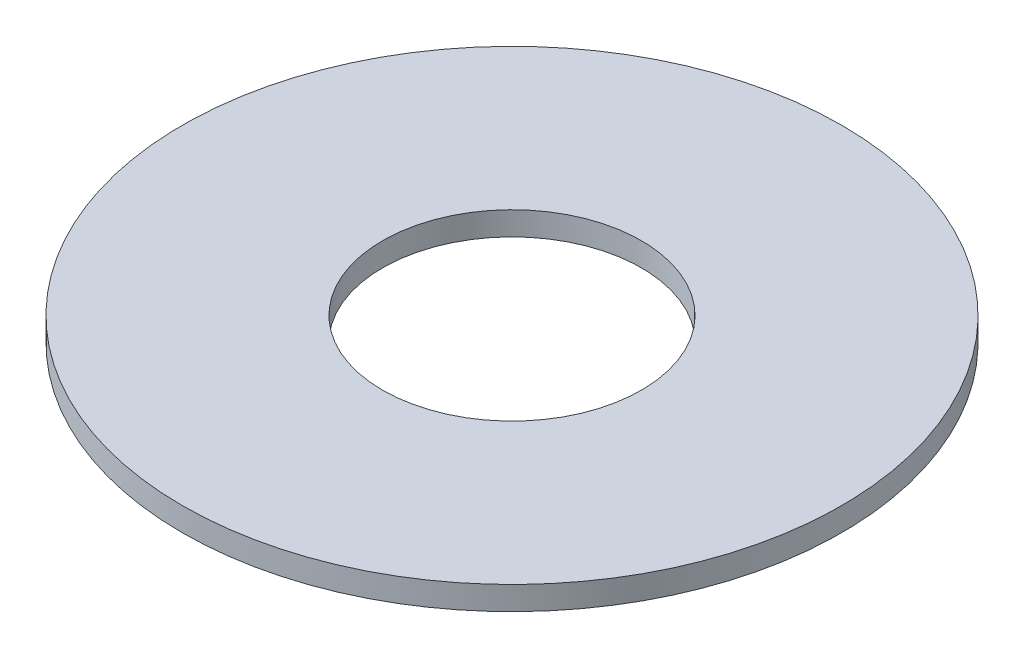
SolidWorks part; units mm, degrees
ref_plane "Front Plane" through (0, 0, 0) normal (0, 0, 1) x (1, 0, 0)
ref_plane "Top Plane" through (0, 0, 0) normal (0, 1, 0) x (1, 0, 0)
ref_plane "Right Plane" through (0, 0, 0) normal (1, 0, 0) x (0, 0, -1)
sketch "Sketch1" plane through (0, 0, 0) normal (0, 1, 0) x (1, 0, 0)
  circle A0 centre (0, 0) radius 70
  dimension "FLANGE_OD" = 140
extrude "Boss-Extrude1" add sketch "Sketch1" along normal blind 5
sketch "Sketch2" plane through (0, 0, 0) normal (0, 1, 0) x (1, 0, 0)
  circle A0 centre (0, 0) radius 27.5
  dimension "BORE_D" = 55
extrude "Cut-Extrude1" cut sketch "Sketch2" along normal through all
sketch "Sketch3" plane through (0, 5, 0) normal (0, 1, 0) x (1, 0, 0)
  circle A0 centre (0, 0) radius 16.1328 construction
  circle A1 centre (-16.1328, 0) radius 3.7211
  dimension "BOLT_D" = 7.4422
  dimension "BOLT_PCD" = 32.2655
extrude "Cut-Extrude2" cut sketch "Sketch3" against normal blind 4.4897 rebuild error yes
pattern_circular "CirPattern1" count 8 over 360 rebuild error yes
